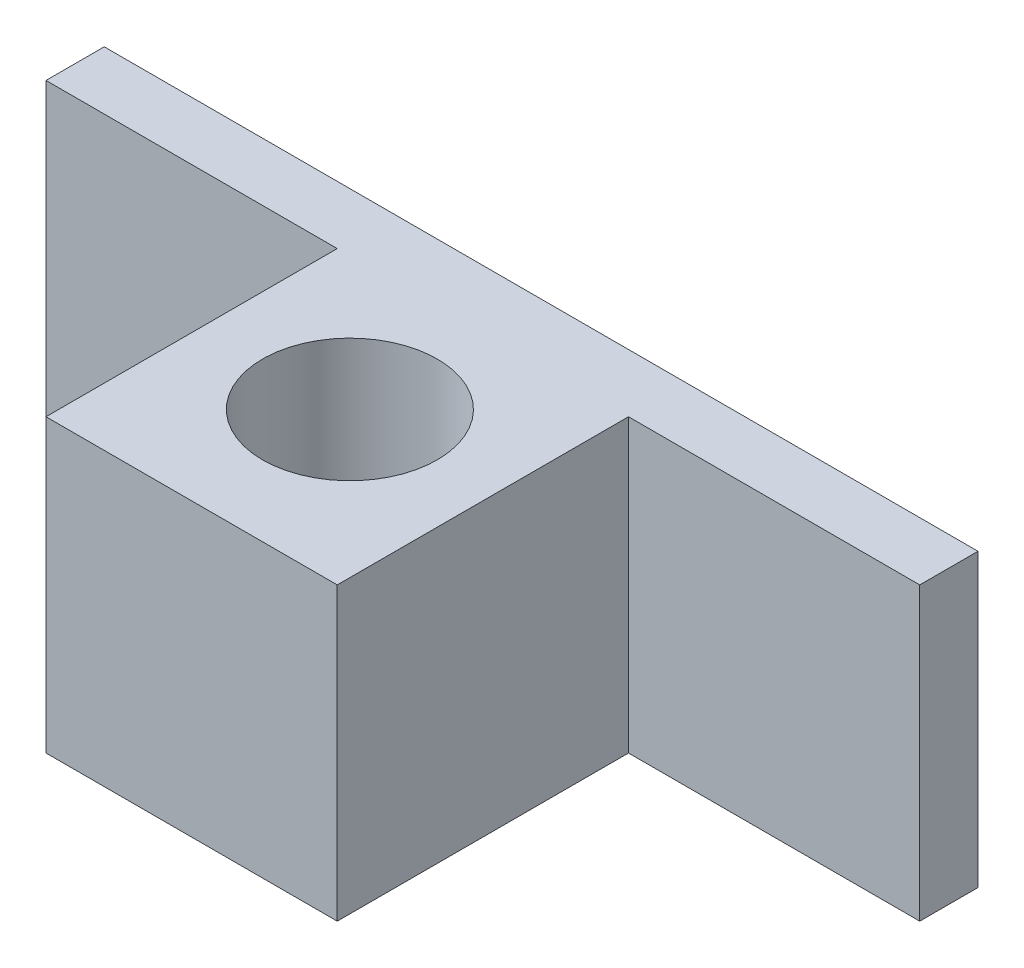
SolidWorks part; units mm, degrees
ref_plane "Front Plane" through (0, 0, 0) normal (1, 0, 0) x (0, 1, 0)
ref_plane "Top Plane" through (0, 0, 0) normal (0, 0, 1) x (0, 1, 0)
ref_plane "Right Plane" through (0, 0, 0) normal (0, 1, 0) x (-1, 0, 0)
sketch "Sketch1" plane through (0, 0, 0) normal (0, 1, 0) x (-1, 0, 0)
  line L0 (-75, 0) -> (75, 0)
  line L1 (75, 0) -> (75, 10)
  line L2 (75, 10) -> (25, 10)
  line L3 (25, 10) -> (25, 60)
  line L4 (25, 60) -> (-25, 60)
  line L5 (-25, 60) -> (-25, 10)
  line L6 (-25, 10) -> (-75, 10)
  line L7 (-75, 10) -> (-75, 0)
  circle A0 centre (0, 32.8284) radius 15
  point P9 (0, 60)
  point P10 (0, 0)
  dimension "D5" = 30
  dimension "D1" = 10
  dimension "D2" = 50
  dimension "D3" = 150
  dimension "D4" = 50
extrude "Boss-Extrude1" add sketch "Sketch1" along normal mid plane 50
